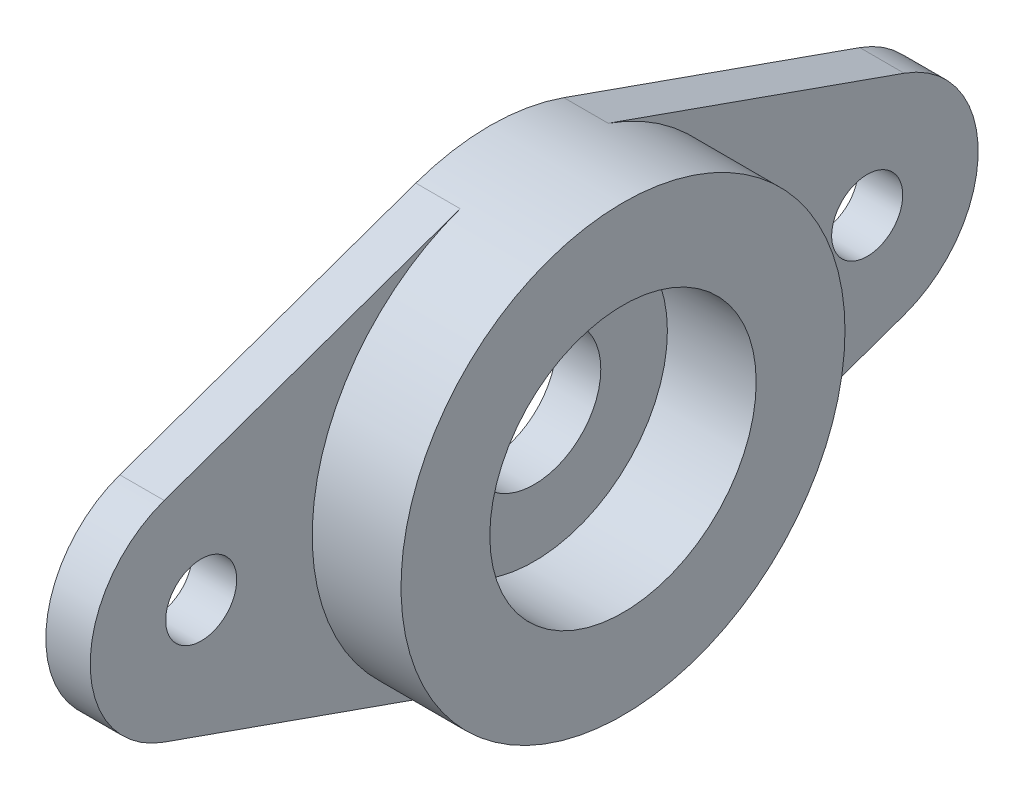
SolidWorks part; units mm, degrees
ref_plane "Front Plane" through (0, 0, 0) normal (0, 0, 1) x (1, 0, 0)
ref_plane "Top Plane" through (0, 0, 0) normal (0, 1, 0) x (1, 0, 0)
ref_plane "Right Plane" through (0, 0, 0) normal (1, 0, 0) x (0, 0, -1)
sketch "Sketch1" plane through (0, 0, 0) normal (1, 0, 0) x (0, 0, -1)
  line L0 (0, 0) -> (0, 7304.3141) construction
  line L1 (-16.6667, 4.714) -> (-3.3333, 9.4281)
  line L2 (-16.6667, -4.714) -> (-3.3333, -9.4281)
  line L3 (16.6667, -4.714) -> (3.3333, -9.4281)
  line L4 (16.6667, 4.714) -> (3.3333, 9.4281)
  circle A2 centre (0, 0) radius 6
  circle A3 centre (0, 0) radius 10
  arc A4 (-16.6667, -4.714) -> (-16.6667, 4.714) centre (-15, 0) cw
  circle A5 centre (-15, 0) radius 1.6
  circle A6 centre (15, 0) radius 1.6
  arc A7 (16.6667, -4.714) -> (16.6667, 4.714) centre (15, 0) ccw
  circle A8 centre (0, 0) radius 3
  dimension "D1" = 12
  dimension "D2" = 10
  dimension "D4" = 3.2
  dimension "D5" = 5
  dimension "D6" = 6
  dimension "D3" = 15
extrude "Boss-Extrude1" add sketch "Sketch1" along normal blind 2 contours A4 L2 A3 L1 A5 | L3 A7 L4 A3 A6 region at (0, 0, 13.2436) region at (0, 0, -13.2436)
extrude "Boss-Extrude2" add sketch "Sketch1<3>" along normal blind 6 contours L0 A3 A2 | A3 L0 A2 region at (0, 9.5772, -1.6432)
sketch "Sketch1<3>" plane through (0, 0, 0) normal (1, 0, 0) x (0, 0, -1) same geometry as "Sketch1"
extrude "Boss-Extrude3" add sketch "Sketch1<4>" along normal blind 2 contours A2 L0 A8 | L0 A2 A8 region at (0, 4.1226, -4.1226)
sketch "Sketch1<4>" plane through (0, 0, 0) normal (1, 0, 0) x (0, 0, -1) same geometry as "Sketch1"
